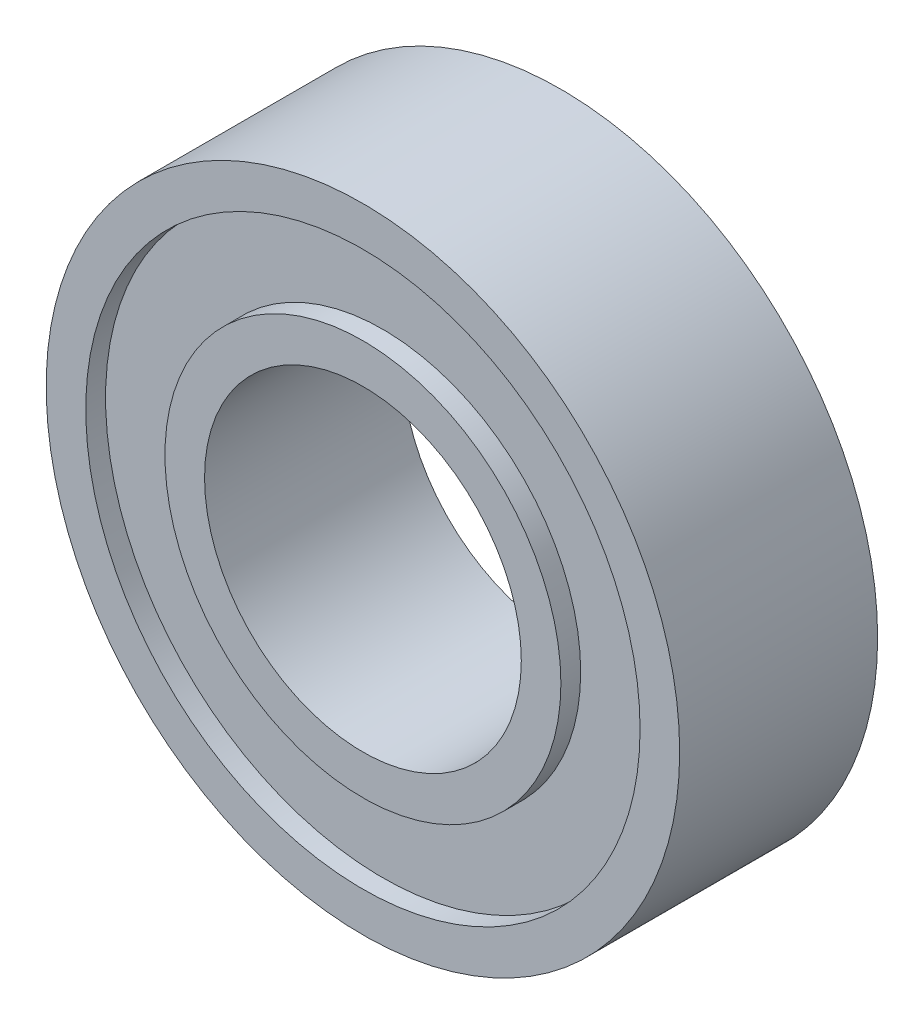
SolidWorks part; units mm, degrees
note: The reader was unsure of these and kept them because the rebuilt part matched: shared geometry of "Esquisse1<3>", "Esquisse1<4>".
ref_plane "Plan de face" through (0, 0, 0) normal (0, 0, 1) x (1, 0, 0)
ref_plane "Plan de dessus" through (0, 0, 0) normal (0, 1, 0) x (1, 0, 0)
ref_plane "Plan de droite" through (0, 0, 0) normal (1, 0, 0) x (0, 0, -1)
sketch "Esquisse1" plane through (0, 0, 0) normal (0, 0, 1) x (1, 0, 0)
  circle A0 centre (0, 0) radius 8
  circle A1 centre (0, 0) radius 7
  circle A2 centre (0, 0) radius 5
  circle A3 centre (0, 0) radius 4
  dimension "D1" = 16
extrude "Boss.-Extru.1" add sketch "Esquisse1" along normal blind 5 contours A0 A1
extrude "Boss.-Extru.2" add sketch "Esquisse1<3>" along normal blind 4.5 contours A1 A2
sketch "Esquisse1<3>" plane through (0, 0, 0) normal (0, 0, 1) x (1, 0, 0) same geometry as "Esquisse1"
extrude "Boss.-Extru.3" add sketch "Esquisse1<4>" along normal blind 5 contours A2 A3
sketch "Esquisse1<4>" plane through (0, 0, 0) normal (0, 0, 1) x (1, 0, 0) same geometry as "Esquisse1"
sketch "Esquisse2" plane through (0, 0, 0) normal (0, 0, -1) x (-1, 0, 0)
  circle A0 centre (0, 0) radius 7
  circle A1 centre (0, 0) radius 5
extrude "Enlèv. mat.-Extru.2" cut sketch "Esquisse2" against normal blind 0.5
